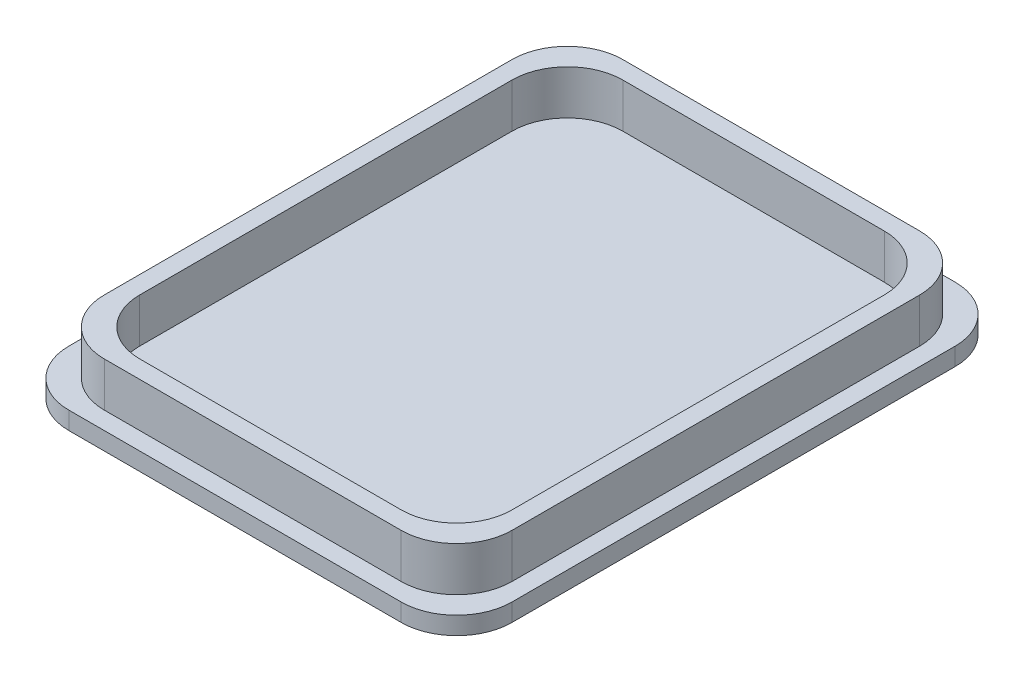
SolidWorks part; units mm, degrees
ref_plane "Спереди" through (0, 0, 0) normal (0, 0, 1) x (1, 0, 0)
ref_plane "Сверху" through (0, 0, 0) normal (0, 1, 0) x (1, 0, 0)
ref_plane "Справа" through (0, 0, 0) normal (1, 0, 0) x (0, 0, -1)
sketch "Sketch1" plane through (0, 0, 0) normal (0, 1, 0) x (1, 0, 0)
  line L1 (-20, -25) -> (20, -25)
  line L2 (-20, -25) -> (-20, 25)
  line L3 (-20, 25) -> (20, 25)
  line L4 (20, -25) -> (20, 25)
  line L5 (-20, -25) -> (20, 25) construction
  line L6 (-20, 25) -> (20, -25) construction
  point P0 (0, 0)
  dimension "D1" = 50
  dimension "D2" = 40
extrude "Boss-Extrude1" add sketch "Sketch1" along normal blind 1.6
sketch "Sketch2" plane through (0, 1.6, 0) normal (0, 1, 0) x (1, 0, 0)
  line L4 (16.8, -21.8) -> (16.8, 21.8)
  line L5 (16.8, 21.8) -> (-16.8, 21.8)
  line L6 (-16.8, 21.8) -> (-16.8, -21.8)
  line L7 (-16.8, -21.8) -> (16.8, -21.8)
  line L8 (18.4, -23.4) -> (18.4, 23.4)
  line L9 (18.4, 23.4) -> (-18.4, 23.4)
  line L10 (-18.4, 23.4) -> (-18.4, -23.4)
  line L11 (-18.4, -23.4) -> (18.4, -23.4)
  line L12 (18.4, -23.4) -> (18.4, 23.4)
  line L13 (18.4, 23.4) -> (-18.4, 23.4)
  line L14 (-18.4, 23.4) -> (-18.4, -23.4)
  line L15 (-18.4, -23.4) -> (18.4, -23.4)
  dimension "D1" = 1.6
  dimension "D2" = 1.6
extrude "Boss-Extrude2" add sketch "Sketch2" along normal blind 4
fillet "Fillet1" radius 5 12 edges at (-16.8, 3.6, 21.8) (16.8, 3.6, 21.8) (16.8, 3.6, -21.8) (-18.4, 3.6, -23.4) (-20, 0.8, 25) (20, 0.8, 25) (20, 0.8, -25) (18.4, 3.6, -23.4) (-18.4, 3.6, 23.4) (18.4, 3.6, 23.4) (-16.8, 3.6, -21.8) (-20, 0.8, -25)
